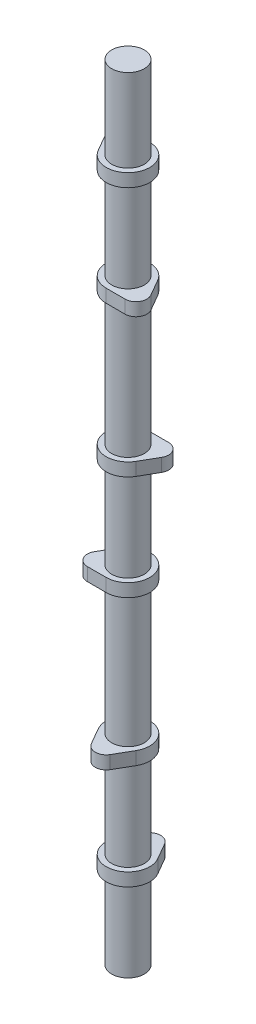
SolidWorks part; units mm, degrees
ref_plane "Front Plane" through (0, 0, 0) normal (0, 0, 1) x (1, 0, 0)
ref_plane "Top Plane" through (0, 0, 0) normal (0, 1, 0) x (1, 0, 0)
ref_plane "Right Plane" through (0, 0, 0) normal (1, 0, 0) x (0, 0, -1)
sketch "Sketch1" plane through (0, 0, 0) normal (0, 1, 0) x (1, 0, 0)
  line L0 (-5.4993, 15.875) -> (-10.9985, 6.35)
  line L1 (5.4993, 15.875) -> (10.9985, 6.35)
  arc A0 (-10.9985, 6.35) -> (10.9985, 6.35) centre (0, 0) ccw
  arc A1 (5.4993, 15.875) -> (-5.4993, 15.875) centre (0, 12.7) ccw
  dimension "D2" = 12.7
  dimension "D3" = 25.4
  dimension "D1" = 12.7
extrude "Boss-Extrude1" add sketch "Sketch1" along normal mid plane 7.62
ref_axis "Axis1" through (0, 140.3866, 0) along (0, -1, 0)
pattern_linear "LPattern1" count 2 spacing 60.96 along (0, 1, 0) of bodies 113
move or copy body "Body-Move/Copy1" bodies to move or copy 114 copy no rotation origin (0, 0, 0) rotation axis (0, 1, 0) rotation angle 180
pattern_linear "LPattern2" count 3 spacing 146.05 along (0, 1, 0) of bodies 113 115
move or copy body "Body-Move/Copy2" bodies to move or copy 116 118 copy no rotation origin (0, 0, 0) rotation axis (0, 1, 0) rotation angle 120
move or copy body "Body-Move/Copy3" bodies to move or copy 119 117 copy no rotation origin (0, 0, 0) rotation axis (0, -1, 0) rotation angle 120
sketch "Sketch2" plane through (0, 0, 0) normal (0, 1, 0) x (1, 0, 0)
  circle A0 centre (0, 0) radius 9.5
  dimension "D1" = 19
extrude "Boss-Extrude2" add sketch "Sketch2" along normal blind 457.15 from offset 52.02 offset against normal yes
